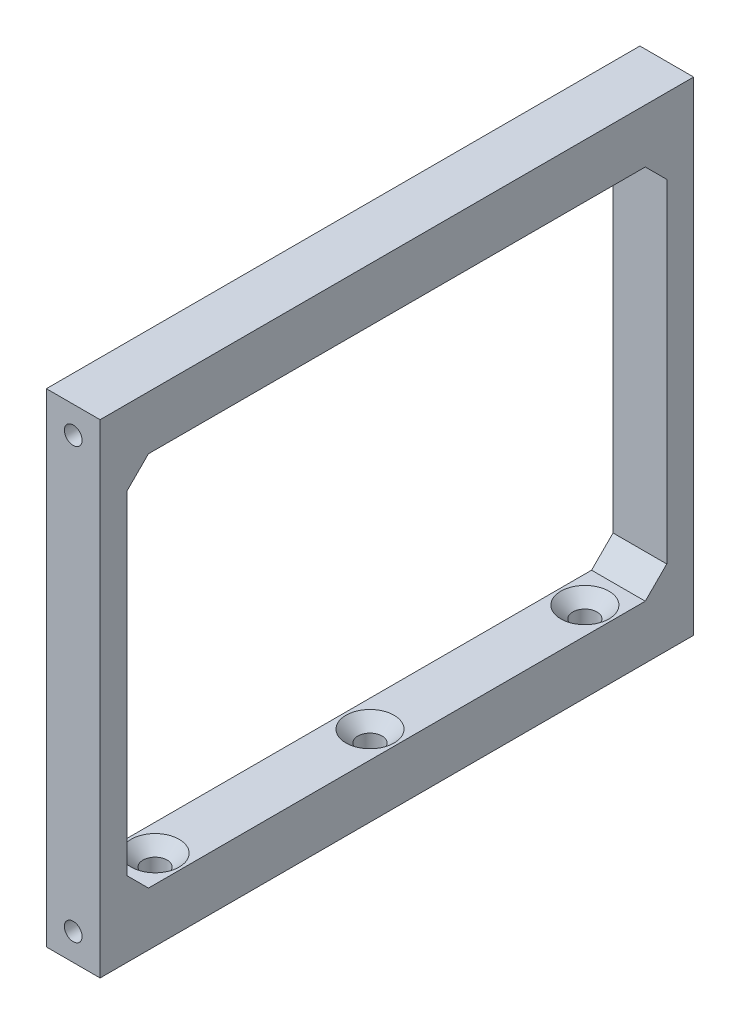
SolidWorks part; units mm, degrees
ref_plane "Front Plane" through (0, 0, 0) normal (0, 0, 1) x (1, 0, 0)
ref_plane "Top Plane" through (0, 0, 0) normal (0, 1, 0) x (1, 0, 0)
ref_plane "Right Plane" through (0, 0, 0) normal (1, 0, 0) x (0, 0, -1)
sketch "Sketch1" plane through (0, 0, 0) normal (1, 0, 0) x (0, 0, -1)
  line L1 (-55.24, -45) -> (55.24, -45)
  line L2 (-55.24, -45) -> (-55.24, 45)
  line L3 (-55.24, 45) -> (55.24, 45)
  line L4 (55.24, -45) -> (55.24, 45)
  line L5 (-55.24, -45) -> (55.24, 45) construction
  line L6 (-55.24, 45) -> (55.24, -45) construction
  line L7 (-50.24, -35) -> (50.24, -35)
  line L8 (-50.24, -35) -> (-50.24, 35)
  line L9 (-50.24, 35) -> (50.24, 35)
  line L10 (50.24, -35) -> (50.24, 35)
  line L11 (-50.24, -35) -> (50.24, 35) construction
  line L12 (-50.24, 35) -> (50.24, -35) construction
  point P0 (0, 0)
  point P6 (0, 0)
  dimension "D1" = 110.48
  dimension "D2" = 90
  dimension "D3" = 5
  dimension "D4" = 10
extrude "Boss-Extrude1" add sketch "Sketch1" along normal blind 10
hole_wizard "M4x0.7 Tapped Hole1" positions "Sketch2" profile "Sketch3" tap size "M4x0.7" standard "ANSI Metric"
sketch "Sketch2" plane through (0, 0, 55.24) normal (0, 0, 1) x (1, 0, 0)
  line L0 (5, 40) -> (5, -40)
  line L2 (10, -45) -> (0, -45) construction
  line L3 (0, 45) -> (0, -45) construction
  point P0 (5, 40)
  point P1 (5, -40)
  dimension "D1" = 80
  dimension "D2" = 5
  dimension "D3" = 5
sketch "Sketch3" plane through (5, 40, 55.24) normal (1, 0, 0) x (0, -1, 0)
  line L0 (0, 0) -> (0, 12.9914)
  line L1 (0, 12.9914) -> (1.65, 12)
  line L2 (1.65, 12) -> (1.65, 0)
  line L5 (1.65, 0) -> (0, 0)
  line L10 (0, 12.9914) -> (-1.65, 12) construction
  line L11 (0, -6.35) -> (0, 107.95) construction
  dimension "Tap Drill Dia." = 3.3
  dimension "Tap Drill Depth" = 12
  dimension "Drill Angle" = 118
cosmetic thread "Hole Thread1" parameters "D1"=8, "D2"=4
cosmetic thread "Hole Thread2" parameters "D1"=8, "D2"=4
hole_wizard "CSK for M4 SFHCS1" positions "Sketch4" profile "Sketch6" countersink size "M4" standard "ANSI Metric"
sketch "Sketch4" plane through (0, -35, 0) normal (0, 1, 0) x (1, 0, 0)
  line L0 (0, 55.24) -> (0, -55.24) construction
  point P0 (5, -40)
  point P12 (5, 0)
  point P13 (5, 40)
  dimension "D1" = 40
  dimension "D2" = 5
  dimension "D3" = 3
sketch "Sketch6" plane through (5, -35, 40) normal (1, 0, 0) x (0, 0, 1)
  line L0 (0, 0) -> (0, 13.3519)
  line L1 (0, 13.3519) -> (2.25, 12)
  line L2 (2.25, 12) -> (2.25, 2.23)
  line L3 (2.25, 2.23) -> (4.48, 0)
  line L5 (4.48, 0) -> (0, 0)
  line L6 (-2.25, 2.23) -> (-4.48, 0) construction
  line L10 (0, 13.3519) -> (-2.25, 12) construction
  line L11 (0, -6.35) -> (0, 107.95) construction
  dimension "Hole Dia." = 4.5
  dimension "Hole Depth" = 12
  dimension "Near C'Sink Dia." = 8.96
  dimension "Near C'Sink Angle" = 90
  dimension "Drill Angle" = 118
mirror "Mirror1" about plane through (0, 0, 0) normal (0, 0, 1) of "M4x0.7 Tapped Hole1"
cosmetic thread "Hole Thread3" parameters "D1"=8, "D2"=4
cosmetic thread "Hole Thread4" parameters "D1"=8, "D2"=4
chamfer "Chamfer1" distance 4 4 edges at (5, -35, -50.24) (5, 35, -50.24) (5, 35, 50.24) (5, -35, 50.24)
sketch "Sketch7" [suppressed] plane through (10, 0, 0) normal (1, 0, 0) x (0, 0, -1)
  line L0 (45.115, 35) -> (-45.115, 35) construction
  line L1 (14.115, -35) -> (19.115, -35)
  line L2 (14.115, -35) -> (14.115, 35)
  line L3 (14.115, 35) -> (19.115, 35)
  line L4 (19.115, -35) -> (19.115, 35)
  line L5 (14.115, -35) -> (19.115, 35) construction
  line L6 (14.115, 35) -> (19.115, -35) construction
  line L7 (-45.115, -35) -> (45.115, -35) construction
  line L8 (49.115, -31) -> (49.115, 31) construction
  point P0 (16.615, 0)
  dimension "D1" = 5
  dimension "D2" = 30
extrude "Boss-Extrude2" [suppressed] add sketch "Sketch7" against normal blind 10
chamfer "Chamfer2" [suppressed] distance 4 angle 45
